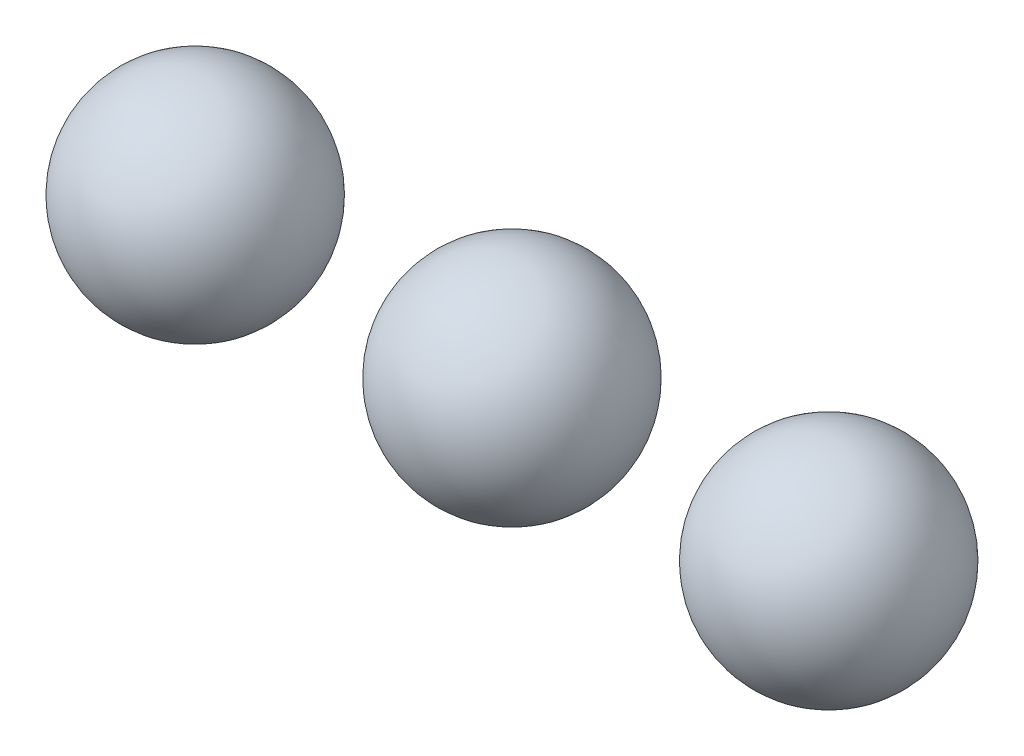
SolidWorks part; units mm, degrees
ref_plane "前视基准面" through (0, 0, 0) normal (0, 0, 1) x (1, 0, 0)
ref_plane "上视基准面" through (0, 0, 0) normal (0, 1, 0) x (1, 0, 0)
ref_plane "右视基准面" through (0, 0, 0) normal (1, 0, 0) x (0, 0, -1)
other "Configuration Table"
sketch "草图1" plane through (0, 0, 0) normal (0, 0, 1) x (1, 0, 0)
  line L0 (0, 20) -> (0, -20) construction
  line L1 (0, 20) -> (0, -20)
  line L2 (60, 20) -> (60, -20)
  line L3 (60, 20) -> (60, -20) construction
  line L4 (120, 20) -> (120, -20)
  line L5 (120, 20) -> (120, -20) construction
  arc A1 (0, 20) -> (0, -20) centre (0, 0) cw
  arc A2 (60, 20) -> (60, -20) centre (60, 0) cw
  arc A3 (120, 20) -> (120, -20) centre (120, 0) cw
  dimension "D1" = 20
  dimension "D2" = 3
revolve "旋转3" add sketch "草图1" angle 360 about L0 region at (8.4883, 0, 0)
revolve "旋转4" add sketch "草图1<4>" angle 360 about L2 region at (68.4883, 0, 0)
sketch "草图1<4>" plane through (0, 0, 0) normal (0, 0, 1) x (1, 0, 0) same geometry as "草图1"
revolve "旋转5" add sketch "草图1<5>" angle 360 about L4 region at (128.4883, 0, 0)
sketch "草图1<5>" plane through (0, 0, 0) normal (0, 0, 1) x (1, 0, 0) same geometry as "草图1"
